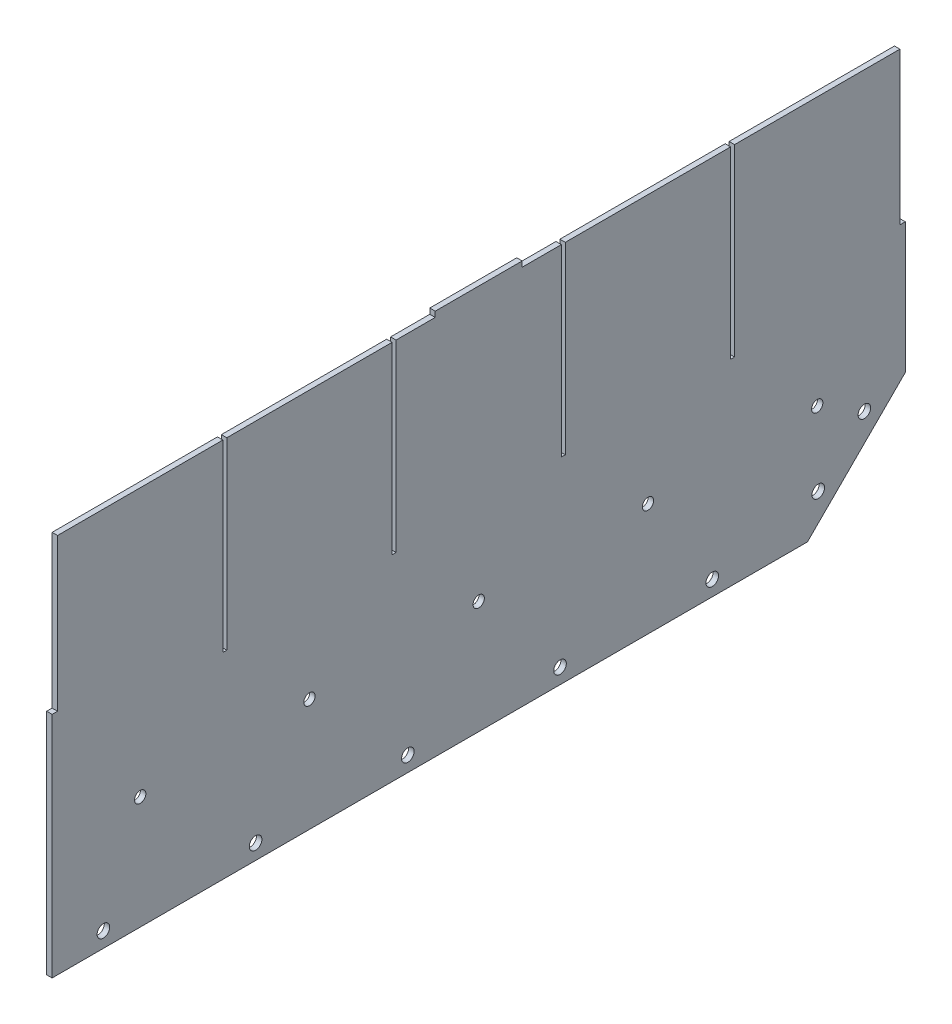
SolidWorks part; units mm, degrees
material "6061-T6 (SS)"
ref_plane "X-Y Datum" through (0, 0, 0) normal (0, 0, 1) x (1, 0, 0)
ref_plane "X-Z Datum" through (0, 0, 0) normal (0, 1, 0) x (1, 0, 0)
ref_plane "Y-Z Datum" through (0, 0, 0) normal (1, 0, 0) x (0, 0, -1)
sketch "Sketch1" plane through (0, 0, 0) normal (1, 0, 0) x (0, 0, -1)
  line L1 (-249.174, 82.55) -> (249.174, 82.55)
  line L2 (-249.174, 82.55) -> (-249.174, -82.55)
  line L3 (-249.174, -82.55) -> (249.174, -82.55)
  line L4 (249.174, 82.55) -> (249.174, -82.55)
  line L5 (-249.174, 82.55) -> (249.174, -82.55) construction
  line L6 (-249.174, -82.55) -> (249.174, 82.55) construction
  point P0 (0, 0)
  dimension "D1" = 165.1
  dimension "D2" = 498.348
extrude "Boss-Extrude1" add sketch "Sketch1" along normal mid plane 3.175
sketch "Sketch2" plane through (1.5875, 0, 0) normal (1, 0, 0) x (0, 0, -1)
  line L3 (192.024, -139.7) -> (-249.174, -139.7)
  line L5 (-249.174, -82.55) -> (249.174, -82.55) construction
  line L6 (-249.174, -82.55) -> (249.174, -82.55)
  line L7 (-249.174, -82.55) -> (-249.174, -139.7)
  line L12 (192.024, -139.7) -> (249.174, -82.55)
  line M10 (-249.174, -82.55) -> (249.174, -82.55)
  dimension "D1" = 45
  dimension "D5" = 57.15
extrude "Boss-Extrude2" add sketch "Sketch2" against normal blind 3.175 contours L3 L12 M10 region at (1.5875, -110.5456, 13.9978)
sketch "Sketch3" plane through (1.5875, 0, 0) normal (1, 0, 0) x (0, 0, -1)
  line L0 (-219.202, -139.7) -> (-219.202, -130.81)
  line L1 (192.024, -139.7) -> (-249.174, -139.7) construction
  line L2 (-219.202, -130.81) -> (-249.174, -130.81)
  line L3 (-249.174, 82.55) -> (-249.174, -139.7) construction
  circle A0 centre (-219.202, -130.81) radius 3.675
  dimension "D1" = 29.972
  dimension "D2" = 8.89
extrude "Cut-Extrude1" cut sketch "Sketch3" against normal blind 3.175 contours L2 A0 L0 | L0 A0 L2 region at (1.5875, -132.3697, 220.7617) region at (1.5875, -130.2901, 218.6821)
pattern_linear "LPattern1" count 5 spacing 88.9 along (0, 0, -1) of "Cut-Extrude1"
sketch "Sketch4" plane through (1.5875, 0, 0) normal (1, 0, 0) x (0, 0, -1)
  line L0 (192.024, -139.7) -> (183.9418, -131.6178)
  line L1 (183.9418, -131.6178) -> (198.3102, -117.2494)
  circle A0 centre (198.3102, -117.2494) radius 3.675
extrude "Cut-Extrude2" cut sketch "Sketch4" against normal through all contours A0 region at (1.5875, -120.5486, -199.6768)
pattern_linear "LPattern2" count 2 spacing 38.1 along (0, 0.7071, -0.7071) of "Cut-Extrude2"
sketch "Sketch5" plane through (-1.5875, 0, 0) normal (-1, 0, 0) x (0, 0, 1)
  line L1 (-249.174, 82.55) -> (-245.999, 82.55)
  line L2 (-249.174, 82.55) -> (-249.174, -6.35)
  line L3 (-249.174, -6.35) -> (-245.999, -6.35)
  line L4 (-245.999, 82.55) -> (-245.999, -6.35)
  line L5 (249.174, 82.55) -> (245.999, 82.55)
  line L6 (249.174, 82.55) -> (249.174, -6.35)
  line L7 (249.174, -6.35) -> (245.999, -6.35)
  line L8 (245.999, 82.55) -> (245.999, -6.35)
  dimension "D1" = 3.175
  dimension "D2" = 88.9
  dimension "D3" = 3.175
  dimension "D4" = 88.9
extrude "Cut-Extrude3" cut sketch "Sketch5" against normal through all
sketch "Sketch6" plane through (-1.5875, 0, 0) normal (-1, 0, 0) x (0, 0, 1)
  line L1 (-149.4282, 82.55) -> (-149.4282, -24.892) construction
  line L2 (-122.174, 82.55) -> (-249.174, 82.55)
  line L3 (-149.4282, 82.55) -> (-149.4282, -24.892)
  line L5 (-149.4282, 82.55) -> (-147.1422, 82.55)
  line L6 (-149.4282, 82.55) -> (-149.4282, -24.892)
  line L7 (-149.4282, -24.892) -> (-147.1422, -24.892)
  line L8 (-147.1422, 82.55) -> (-147.1422, -24.892)
  dimension "D1" = 2.286
  dimension "D2" = 107.442
extrude "Cut-Extrude4" cut sketch "Sketch6" against normal through all contours L8 L2 L3 L7 region at (-1.5875, 28.829, -148.2852)
pattern_linear "LPattern3" count 4 spacing 98.8568 along (0, 0, 1) of "Cut-Extrude4"
sketch "Sketch7" plane through (-1.5875, 0, 0) normal (-1, 0, 0) x (0, 0, 1)
  line L0 (122.174, 85.725) -> (25.4, 85.725) construction
  line L1 (25.4, 82.55) -> (-25.4, 82.55)
  line L2 (25.4, 82.55) -> (25.4, 85.725)
  line L3 (25.4, 85.725) -> (-25.4, 85.725)
  line L4 (-25.4, 82.55) -> (-25.4, 85.725)
  line L5 (25.4, 82.55) -> (-25.4, 85.725) construction
  line L6 (25.4, 85.725) -> (-25.4, 82.55) construction
  point P0 (0, 84.1375)
  dimension "D1" = 3.175
  dimension "D2" = 50.8
extrude "Boss-Extrude3" add sketch "Sketch7" against normal blind 3.175
sketch "Sketch8" plane through (1.5875, 0, 0) normal (1, 0, 0) x (0, 0, -1)
  line L0 (192.024, -139.7) -> (-249.174, -139.7) construction
  circle A0 centre (0, -73.8124) radius 3
  dimension "D1" = 6
  dimension "D2" = 65.8876
hole_wizard "M6 Clearance Hole1" positions "Sketch9" profile "Sketch10" hole size "M6" standard "ANSI Metric" end condition through all
sketch "Sketch9" plane through (1.5875, 0, 0) normal (1, 0, 0) x (0, 0, -1)
  point P0 (0, -73.8124)
sketch "Sketch10" plane through (1.5875, -73.8124, 0) normal (0, 1, 0) x (0, 0, -1)
  line L0 (0, 0) -> (0, 3.175)
  line L1 (0, 3.175) -> (3.3, 3.175)
  line L2 (3.3, 3.175) -> (3.3, 0)
  line L5 (3.3, 0) -> (0, 0)
  line L11 (0, -6.35) -> (0, 107.95) construction
  dimension "Thru Hole Dia." = 6.6
  dimension "Thru Hole Depth" = 3.175
pattern_linear "LPattern4" count 3 spacing 98.8568 along (0, 0, 1) count 3 spacing 98.8568 along (0, 0, -1) of "M6 Clearance Hole1"
